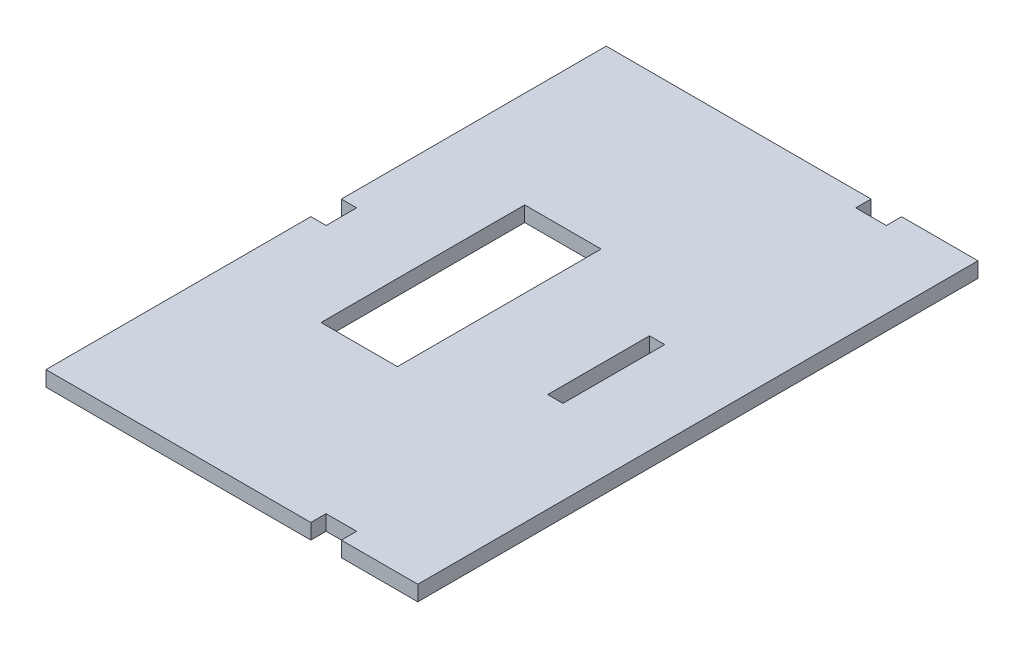
SolidWorks part; units mm, degrees
ref_plane "Спереди" through (0, 0, 0) normal (0, 0, 1) x (1, 0, 0)
ref_plane "Сверху" through (0, 0, 0) normal (0, 1, 0) x (1, 0, 0)
ref_plane "Справа" through (0, 0, 0) normal (1, 0, 0) x (0, 0, -1)
other "Configuration Table"
sketch "Эскиз4" plane through (0, 0, 0) normal (0, 1, 0) x (1, 0, 0)
  line L0 (0, 58) -> (0, 110)
  line L1 (0, 0) -> (52, 0)
  line L2 (0, 0) -> (0, 52)
  line L3 (0, 110) -> (52, 110)
  line L6 (55, 107) -> (52, 107)
  line L7 (52, 107) -> (55, 107)
  line L8 (55, 107) -> (58, 107)
  line L9 (52, 107) -> (52, 110)
  line L10 (58, 107) -> (58, 110)
  line L11 (58, 3) -> (58, 0)
  line L12 (55, 3) -> (58, 3)
  line L13 (55, 3) -> (52, 3)
  line L14 (52, 3) -> (52, 0)
  line L15 (3, 55) -> (3, 58)
  line L16 (3, 55) -> (3, 52)
  line L17 (3, 58) -> (0, 58)
  line L18 (3, 52) -> (0, 52)
  line L22 (58, 0) -> (73, 0)
  line L24 (58, 110) -> (73, 110)
  line L25 (55, 107) -> (55, 3) construction
  line L26 (3, 55) -> (73, 55)
  line L27 (73, 110) -> (73, 0)
  point P28 (73.1105, 55)
  dimension "D1" = 3
  dimension "D2" = 3
  dimension "D3" = 3
  dimension "D4" = 15
  dimension "D5" = 3
  dimension "D6" = 3
  dimension "D7" = 3
extrude "Бобышка-Вытянуть3" add sketch "Эскиз4" along normal blind 3 contours L3 L10 L8 L6 L9 L2 L17 L15 L16 L18 L1 L14 L13 L12 L11 | L25 L6 L9 L3 L0 L17 L15 L26 | L8 L25 L26 L27 L24 L10 | L26 L25 L12 L11 L22 L27 region at (27.5, 0, -82.5) region at (27.5, 0, -27.5) region at (64.0688, 0, -27.7385) region at (64.0688, 0, -82.2615)
sketch "Sketch1" plane through (0, 3, 0) normal (0, 1, 0) x (1, 0, 0)
  line L0 (3, 52) -> (3, 58) construction
  line L13 (3, 55) -> (107, 55) construction
  line L15 (55, 107) -> (55, 3) construction
  line L16 (52, 107) -> (58, 107) construction
  line L17 (58, 3) -> (52, 3) construction
  line L19 (19, 75) -> (34, 75)
  line L20 (19, 75) -> (19, 35)
  line L21 (19, 35) -> (34, 35)
  line L22 (34, 75) -> (34, 35)
  line L23 (53.5, 65) -> (56.5, 65)
  line L24 (53.5, 65) -> (53.5, 45)
  line L25 (53.5, 45) -> (56.5, 45)
  line L26 (56.5, 65) -> (56.5, 45)
  point P8 (0, 0)
  dimension "D1" = 3
  dimension "D2" = 20
  dimension "D3" = 16
  dimension "D4" = 15
  dimension "D5" = 40
extrude "Cut-Extrude1" cut sketch "Sketch1" against normal blind 10
